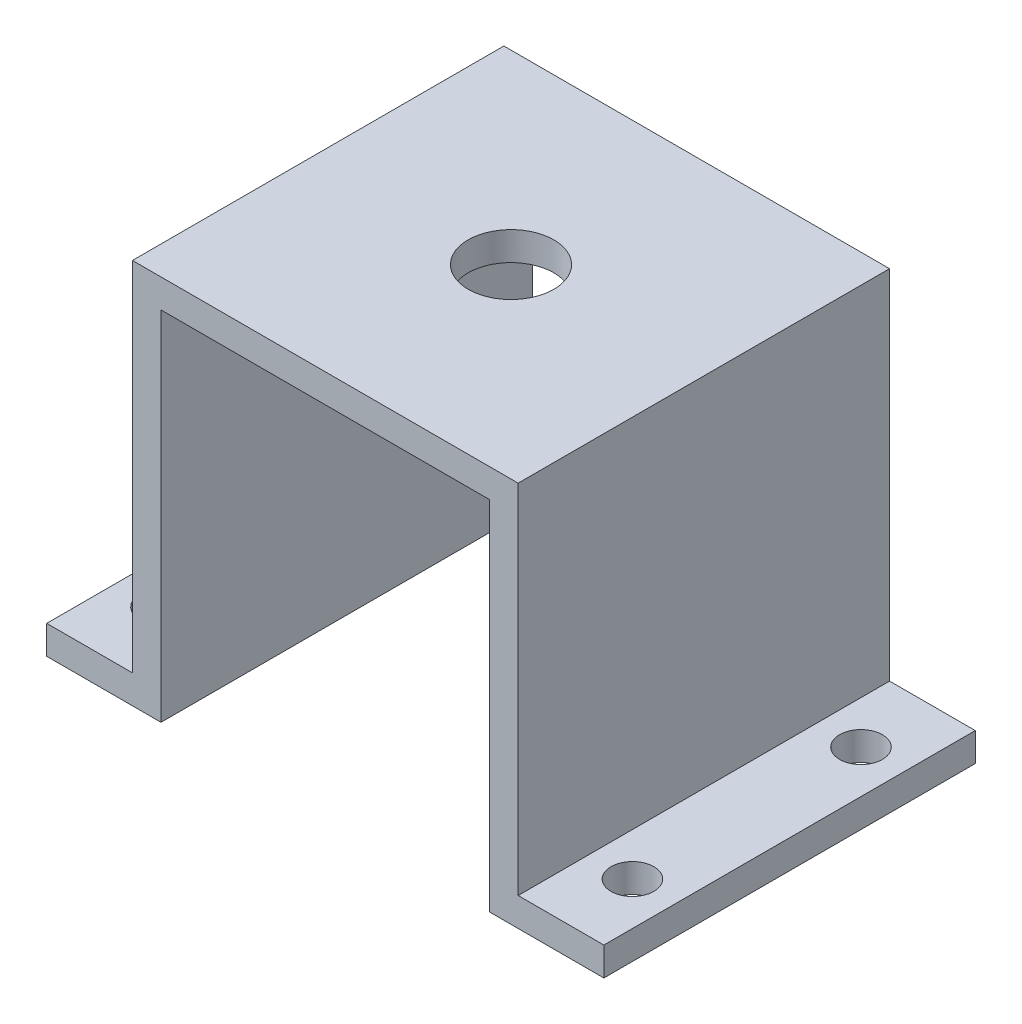
SolidWorks part; units mm, degrees
ref_plane "Plan de face" through (0, 0, 0) normal (0, 0, 1) x (1, 0, 0)
ref_plane "Plan de dessus" through (0, 0, 0) normal (0, 1, 0) x (1, 0, 0)
ref_plane "Plan de droite" through (0, 0, 0) normal (1, 0, 0) x (0, 0, -1)
sketch "Esquisse1" plane through (0, 0, 0) normal (0, 0, 1) x (1, 0, 0)
  line L0 (-8, 0) -> (0, 0)
  line L1 (0, 0) -> (0, 25)
  line L2 (0, 25) -> (23, 25)
  line L3 (23, 25) -> (23, 0)
  line L4 (31, 0) -> (23, 0)
  dimension "D1" = 8
  dimension "D2" = 23
  dimension "D3" = 25
extrude "Extru.-Mince1" add sketch "Esquisse1" along normal blind 26 thin thin type one direction wall 2
ref_point "Centre face"
sketch "Esquisse4" plane through (0, 27, 0) normal (0, 1, 0) x (1, 0, 0)
  circle A1 centre (11.5, -13) radius 3
  dimension "D1" = 6
extrude "Extrusion1" cut sketch "Esquisse4" against normal up to next
ref_axis "Axe3" through (-5, 2, 0) along (0, 0, 1)
ref_axis "Axe4" through (-2, 2, 13) along (-1, 0, 0)
ref_axis "Axe5" through (28, 2, 26) along (0, 0, -1)
ref_axis "Axe6" through (31, 2, 13) along (-1, 0, 0)
sketch "Esquisse5" plane through (0, 2, 0) normal (0, 1, 0) x (1, 0, 0)
  line L2 (-5, 0) -> (-5, -26) construction
  line L4 (-2, 0) -> (-8, 0) construction
  line L5 (-2, -26) -> (-8, -26) construction
  circle A0 centre (-5, -21) radius 1.5
  circle A1 centre (-5, -5) radius 1.5
  dimension "D3" = 3
  dimension "D1" = 5
  dimension "D2" = 5
extrude "Extrusion2" cut sketch "Esquisse5" against normal up to next
ref_plane "Plan2" through (11.5, 27, 26) normal (-1, 0, 0) x (0, 0, 1)
mirror "Symétrie1" about plane through (11.5, 27, 26) normal (-1, 0, 0) of "Extrusion2"
